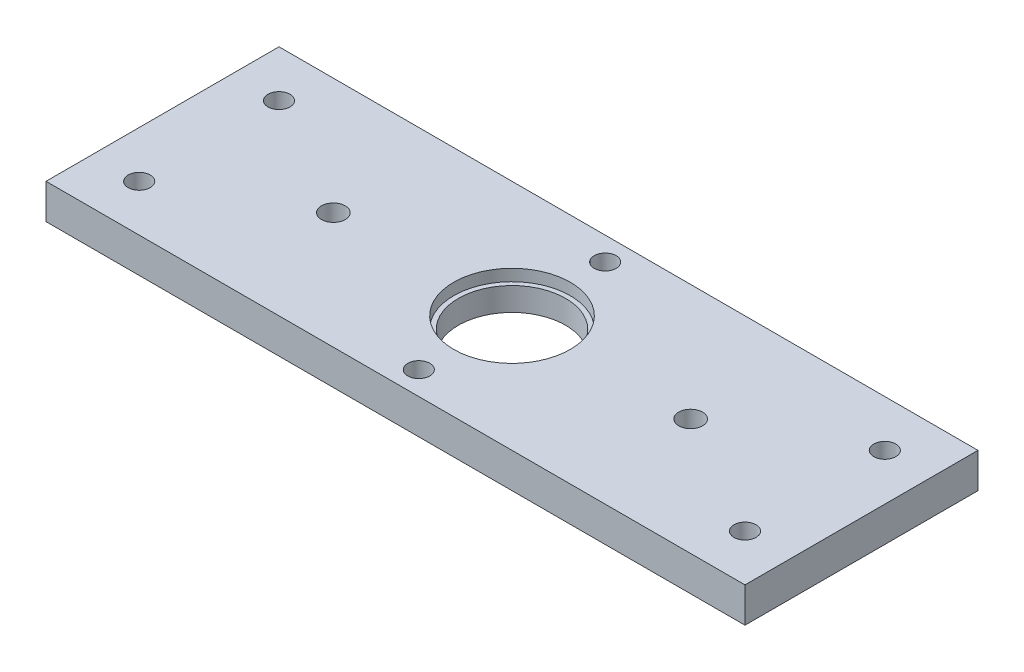
SolidWorks part; units mm, degrees
ref_plane "Front Plane" through (0, 0, 0) normal (0, 0, 1) x (1, 0, 0)
ref_plane "Top Plane" through (0, 0, 0) normal (0, 1, 0) x (1, 0, 0)
ref_plane "Right Plane" through (0, 0, 0) normal (1, 0, 0) x (0, 0, -1)
sketch "Sketch1" plane through (0, 0, 0) normal (0, 1, 0) x (1, 0, 0)
  line L1 (-95.25, -31.75) -> (95.25, -31.75)
  line L2 (-95.25, -31.75) -> (-95.25, 31.75)
  line L3 (-95.25, 31.75) -> (95.25, 31.75)
  line L4 (95.25, -31.75) -> (95.25, 31.75)
  line L5 (-95.25, -31.75) -> (95.25, 31.75) construction
  line L6 (-95.25, 31.75) -> (95.25, -31.75) construction
  point P0 (0, 0)
  dimension "D1" = 190.5
  dimension "D2" = 63.5
extrude "Boss-Extrude1" add sketch "Sketch1" along normal blind 9.525
sketch "Sketch2" plane through (0, 9.525, 0) normal (0, 1, 0) x (1, 0, 0)
  line L0 (-31.75, -31.75) -> (-31.75, 31.75)
  line L1 (-95.25, -31.75) -> (95.25, -31.75) construction
  line L2 (95.25, 31.75) -> (-95.25, 31.75) construction
  line L3 (-95.25, 31.75) -> (-95.25, -31.75) construction
  line L4 (31.75, 31.75) -> (31.75, -31.75)
  line L5 (95.25, -31.75) -> (95.25, 31.75) construction
  dimension "D1" = 63.5
  dimension "D2" = 63.5
sketch "Sketch3" plane through (0, 9.525, 0) normal (0, 1, 0) x (1, 0, 0)
  circle A0 centre (0, 0) radius 14.605
  dimension "D1" = 29.21
extrude "Cut-Extrude1" cut sketch "Sketch3" against normal through all
sketch "Sketch6" plane through (0, 0, 31.75) normal (0, 0, 1) x (1, 0, 0)
  line L0 (-31.75, 9.525) -> (-31.75, 0)
  line L1 (-95.25, 0) -> (95.25, 0) construction
sketch "Sketch7" plane through (0, 0, 0) normal (0, -1, 0) x (1, 0, 0)
  line L0 (-31.75, 31.75) -> (-31.75, -31.75)
  line L1 (95.25, -31.75) -> (-95.25, -31.75) construction
sketch "Sketch8" plane through (0, 0, 31.75) normal (0, 0, 1) x (1, 0, 0)
  line L0 (31.75, 9.525) -> (31.75, 0)
  line L1 (-95.25, 0) -> (95.25, 0) construction
sketch "Sketch9" plane through (0, 0, 0) normal (0, -1, 0) x (1, 0, 0)
  line L0 (31.75, 31.75) -> (31.75, -31.75)
  line L1 (95.25, -31.75) -> (-95.25, -31.75) construction
hole_wizard "Ø6.0 (6) Diameter Hole1" positions "Sketch22" profile "Sketch23" hole size "Ø6.0" standard "ANSI Metric" end condition through all
sketch "Sketch22" plane through (0, 0, 0) normal (0, -1, 0) x (-1, 0, 0)
  point P0 (0, -25.4)
  point P2 (0, 25.4)
  dimension "D1" = 25.4
  dimension "D2" = 25.4
sketch "Sketch23" plane through (0, 0, 25.4) normal (1, 0, 0) x (0, 0, -1)
  line L0 (0, 0) -> (0, 9.525)
  line L1 (0, 9.525) -> (3, 9.525)
  line L2 (3, 9.525) -> (3, 0)
  line L5 (3, 0) -> (0, 0)
  line L11 (0, -6.35) -> (0, 107.95) construction
  dimension "Thru Hole Dia." = 6
  dimension "Thru Hole Depth" = 9.525
hole_wizard "Ø6.5 (6.5) Diameter Hole3" positions "Sketch24" profile "Sketch25" hole size "Ø6.5" standard "ANSI Metric" end condition through all
sketch "Sketch24" plane through (0, 0, 0) normal (0, -1, 0) x (-1, 0, 0)
  line L0 (31.75, -31.75) -> (31.75, 31.75) construction
  line L1 (-31.75, 31.75) -> (-31.75, -31.75) construction
  point P0 (48.6833, 0)
  point P2 (-48.6833, 0)
  dimension "D1" = 16.9333
  dimension "D2" = 16.9333
sketch "Sketch25" plane through (-48.6833, 0, 0) normal (1, 0, 0) x (0, 0, -1)
  line L0 (0, 0) -> (0, 9.525)
  line L1 (0, 9.525) -> (3.25, 9.525)
  line L2 (3.25, 9.525) -> (3.25, 0)
  line L5 (3.25, 0) -> (0, 0)
  line L11 (0, -6.35) -> (0, 107.95) construction
  dimension "Thru Hole Dia." = 6.5
  dimension "Thru Hole Depth" = 9.525
sketch "Sketch29" plane through (0, 9.525, 0) normal (0, 1, 0) x (1, 0, 0)
  circle A0 centre (0, 0) radius 15.875
extrude "Cut-Extrude5" cut sketch "Sketch29" against normal blind 3.175
hole_wizard "Ø6.0 (6) Diameter Hole3" positions "Sketch32" profile "Sketch31" hole size "Ø6.0" standard "ANSI Metric" end condition through all
sketch "Sketch32" plane through (0, 9.525, 0) normal (0, 1, 0) x (1, 0, 0)
  line L0 (95.25, 31.75) -> (-95.25, 31.75) construction
  line L1 (-95.25, 31.75) -> (-95.25, -31.75) construction
  line L2 (-95.25, -31.75) -> (95.25, -31.75) construction
  line L3 (95.25, -31.75) -> (95.25, 31.75) construction
  point P0 (-82.55, 19.05)
  point P2 (-82.55, -19.05)
  point P4 (82.55, -19.05)
  point P6 (82.55, 19.05)
  dimension "D1" = 12.7
  dimension "D2" = 12.7
  dimension "D3" = 12.7
  dimension "D4" = 12.7
  dimension "D5" = 12.7
  dimension "D6" = 12.7
  dimension "D7" = 12.7
  dimension "D8" = 12.7
sketch "Sketch31" plane through (-82.55, 9.525, -19.05) normal (1, 0, 0) x (0, 0, 1)
  line L0 (0, 0) -> (0, 9.525)
  line L1 (0, 9.525) -> (3, 9.525)
  line L2 (3, 9.525) -> (3, 0)
  line L5 (3, 0) -> (0, 0)
  line L11 (0, -6.35) -> (0, 107.95) construction
  dimension "Thru Hole Dia." = 6
  dimension "Thru Hole Depth" = 9.525
